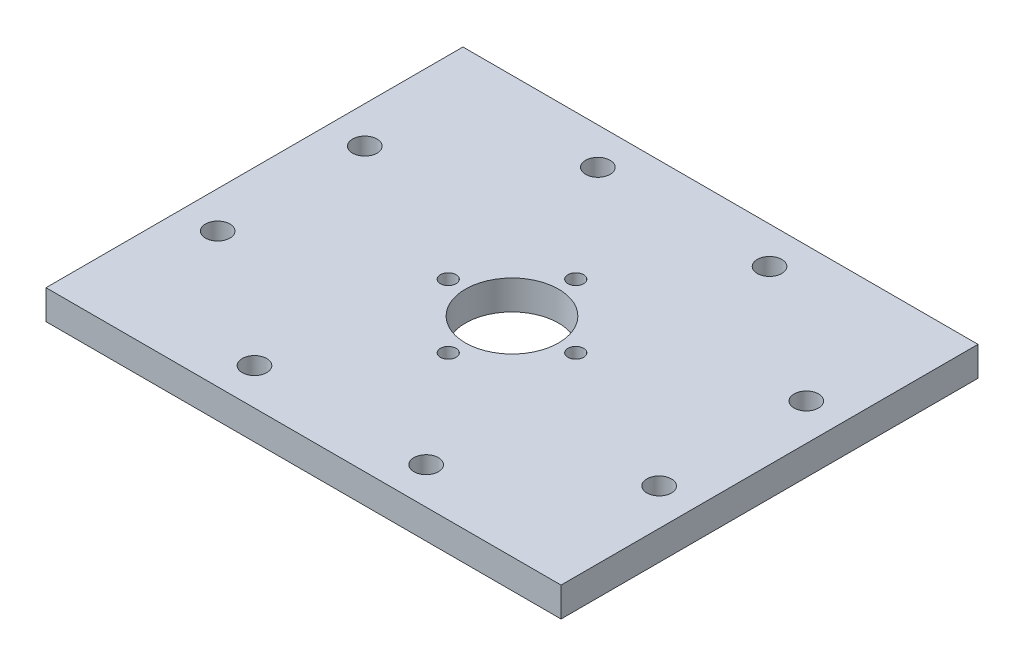
SolidWorks part; units mm, degrees
ref_plane "Front Plane" through (0, 0, 0) normal (0, 0, 1) x (1, 0, 0)
ref_plane "Top Plane" through (0, 0, 0) normal (0, 1, 0) x (1, 0, 0)
ref_plane "Right Plane" through (0, 0, 0) normal (1, 0, 0) x (0, 0, -1)
sketch "Sketch1" plane through (0, 0, 0) normal (0, 1, 0) x (1, 0, 0)
  line L0 (0, -46.75) -> (0, 46.75) construction
  line L1 (-52.5, 42.5) -> (52.5, 42.5)
  line L2 (-52.5, 42.5) -> (-52.5, -42.5)
  line L3 (-52.5, -42.5) -> (52.5, -42.5)
  line L4 (52.5, 42.5) -> (52.5, -42.5)
  line L5 (-52.5, 42.5) -> (52.5, -42.5) construction
  line L6 (-52.5, -42.5) -> (52.5, 42.5) construction
  line L7 (-52.25, 0) -> (52.25, 0) construction
  circle A0 centre (0, 0) radius 13 construction
  circle A1 centre (0, 13) radius 1.5 construction
  circle A2 centre (13, 0) radius 1.5 construction
  circle A3 centre (0, -13) radius 1.5 construction
  circle A4 centre (-13, 0) radius 1.5 construction
  circle A7 centre (0, 0) radius 9.5
  circle A8 centre (-17.5, 35) radius 2.5
  circle A9 centre (17.5, 35) radius 2.5
  circle A10 centre (17.5, -35) radius 2.5
  circle A11 centre (-17.5, -35) radius 2.5
  circle A12 centre (-45, 15) radius 2.5
  circle A13 centre (-45, -15) radius 2.5
  circle A14 centre (45, -15) radius 2.5
  circle A15 centre (45, 15) radius 2.5
  dimension "D1" = 26
  dimension "D2" = 3
  dimension "D4" = 19
  dimension "D7" = 5
  dimension "D10" = 5
  dimension "D5" = 17.5
  dimension "D6" = 105
  dimension "D8" = 85
  dimension "D9" = 35
  dimension "D11" = 45
  dimension "D12" = 15
  dimension "D3" = 4
extrude "Boss-Extrude1" add sketch "Sketch1" along normal blind 6
hole_wizard "CSK for M3 Flat Head Machine Screw1" positions "Sketch7" profile "Sketch8" countersink size "M3" standard "ANSI Metric" end condition through all
sketch "Sketch7" plane through (0, 0, 0) normal (0, -1, 0) x (-1, 0, 0)
  point P0 (-13, 0)
  point P3 (0, -13)
  point P6 (13, 0)
  point P9 (0, 13)
sketch "Sketch8" plane through (13, 0, 0) normal (1, 0, 0) x (0, 0, -1)
  line L0 (0, 0) -> (0, 6)
  line L1 (0, 6) -> (1.6, 6)
  line L2 (1.6, 6) -> (1.6, 1.55)
  line L3 (1.6, 1.55) -> (3.15, 0)
  line L5 (3.15, 0) -> (0, 0)
  line L6 (-1.6, 1.55) -> (-3.15, 0) construction
  line L11 (0, -6.35) -> (0, 107.95) construction
  dimension "Thru Hole Dia." = 3.2
  dimension "Thru Hole Depth" = 6
  dimension "Near C'Sink Dia." = 6.3
  dimension "Near C'Sink Angle" = 90
sketch "Sketch9" plane through (0, 0, 0) normal (0, 1, 0) x (1, 0, 0)
  line L0 (0, -3.3) -> (0, 3.3) construction
  line L1 (-3.3, 0) -> (3.3, 0) construction
  circle A0 centre (17.5, 35) radius 6
  circle A1 centre (-17.5, 35) radius 6
  circle A2 centre (-17.5, -35) radius 6
  circle A3 centre (17.5, -35) radius 6
  dimension "D1" = 12
equation "\"testbed_height\" = 91.50mm"
equation "\"plate_thickness\" = 6mm"
equation "\"main_body_splay_length\" = 48.5mm"
equation "\"splay_shaft_length_no_wires\" = 10mm"
equation "\"splay_shaft_length_wires\" = 6.5mm"
equation "\"timing_pulley_offset\" = 0mm"
equation "\"effective_motor_length\" = \"timing_pulley_offset\" + \"splay_shaft_length_no_wires\" + \"main_body_splay_length\""
equation "\"80_20_side\" = 25.4mm"
equation "\"80_20_length\" = 152.4mm"
equation "\"80_20_optic_mount_length\" = \"80_20_length\" - 25.4mm"
equation "\"optic_board_hole_size\" = 6.35mm"
equation "\"total_mounting_length\" = \"testbed_height\" - \"effective_motor_length\" - \"80_20_side\""
equation "\"mounting_vertical_portion_height\" = \"total_mounting_length\" - 2 * \"plate_thickness\""
equation "\"face_mount_width\" = 15.25mm"
equation "\"center_dist_to_face_mount_vertical_screws\" = 5mm"
equation "\"D1@Boss-Extrude1\"=\"plate_thickness\""
